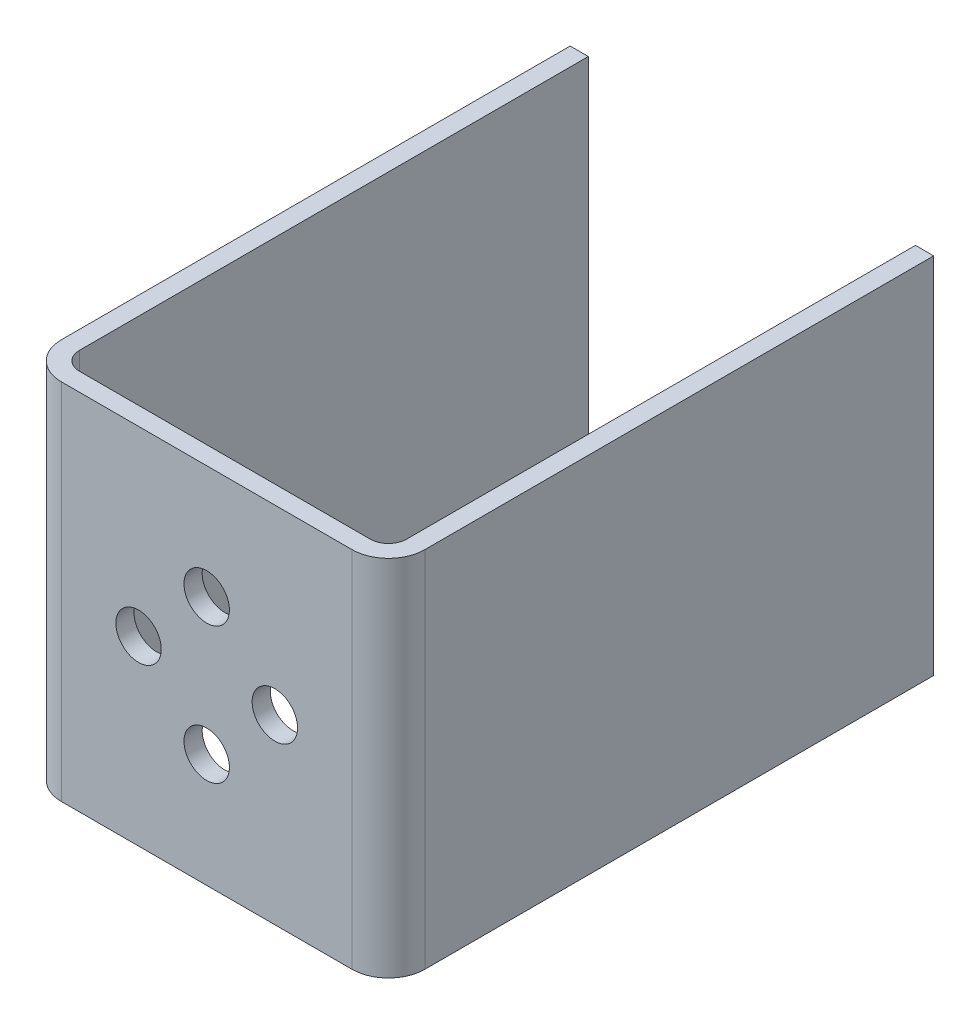
SolidWorks part; units mm, degrees
ref_plane "Front Plane" through (0, 0, 0) normal (0, 0, 1) x (1, 0, 0)
ref_plane "Top Plane" through (0, 0, 0) normal (0, 1, 0) x (1, 0, 0)
ref_plane "Right Plane" through (0, 0, 0) normal (1, 0, 0) x (0, 0, -1)
sketch "Sketch1" plane through (0, 0, 0) normal (0, 1, 0) x (1, 0, 0)
  line L0 (0, 76.2) -> (2.54, 76.2)
  line L1 (5.08, 0) -> (45.72, 0)
  line L2 (0, 5.08) -> (0, 76.2)
  line L4 (50.8, 5.08) -> (50.8, 76.2)
  line L5 (2.54, 76.2) -> (2.54, 5.08)
  line L6 (5.08, 2.54) -> (45.72, 2.54)
  line L7 (48.26, 5.08) -> (48.26, 76.2)
  line L8 (48.26, 76.2) -> (50.8, 76.2)
  line L9 (2.54, 2.54) -> (2.54, 0) construction
  arc A0 (45.72, 0) -> (50.8, 5.08) centre (45.72, 5.08) ccw
  arc A1 (5.08, 0) -> (0, 5.08) centre (5.08, 5.08) cw
  arc A2 (45.72, 2.54) -> (48.26, 5.08) centre (45.72, 5.08) ccw
  arc A3 (2.54, 5.08) -> (5.08, 2.54) centre (5.08, 5.08) ccw
  point P14 (50.8, 0)
  point P17 (0, 0)
  dimension "D4" = 5.08
  dimension "D5" = 5.08
  dimension "D6" = 2.54
  dimension "D7" = 2.54
  dimension "D1" = 76.2
  dimension "D2" = 50.8
  dimension "D3" = 2.54
extrude "Boss-Extrude1" add sketch "Sketch1" along normal blind 50.8
sketch "Sketch2" plane through (0, 0, -2.54) normal (0, 0, -1) x (-1, 0, 0)
  line L0 (-50.8, 50.8) -> (0, 0) construction
  line L1 (-25.4, 25.4) -> (-34.925, 25.4) construction
  line L2 (-25.4, 25.4) -> (-25.4, 34.925) construction
  line L3 (-25.4, 25.4) -> (-15.875, 25.4) construction
  line L4 (-25.4, 25.4) -> (-25.4, 15.875) construction
  circle A0 centre (-34.925, 25.4) radius 3.175
  circle A1 centre (-25.4, 34.925) radius 3.175
  circle A2 centre (-15.875, 25.4) radius 3.175
  circle A3 centre (-25.4, 15.875) radius 3.175
  point P8 (-25.4, 25.4)
  point P16 (-25.4, 25.4)
  dimension "D1" = 6.35
  dimension "D2" = 9.525
  dimension "D3" = 4
ref_axis "Axis1" through (25.4, 25.4, -2.54) along (0, 0, 1)
extrude "Cut-Extrude2" cut sketch "Sketch2" against normal through all
equation "\"BendRadius\"= .2"
equation "\"D5@Sketch1\"= \"BendRadius\""
equation "\"D4@Sketch1\"=\"BendRadius\""
equation "\"MetalThickness\"= .1"
equation "\"D3@Sketch1\"=\"MetalThickness\""
equation "\"D7@Sketch1\"=\"BendRadius\"-\"MetalThickness\""
equation "\"D6@Sketch1\"=\"BendRadius\"-\"MetalThickness\""
equation "\"Width\"= 2"
equation "\"D1@Boss-Extrude1\"=\"Width\""
equation "\"D2@Sketch1\"=\"Width\""
equation "\"Height\"= 3"
equation "\"D1@Sketch1\"=\"Height\""
